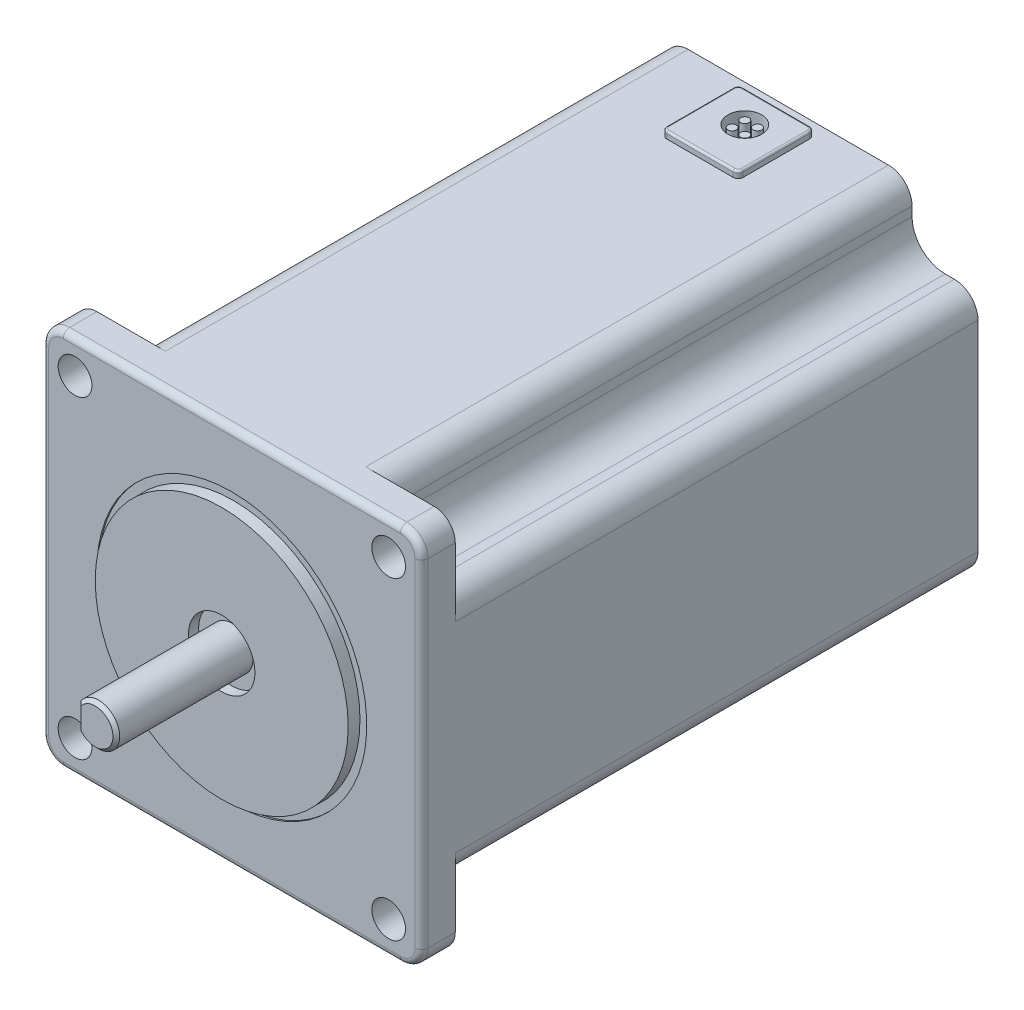
SolidWorks part; units mm, degrees
ref_plane "Front Plane" through (0, 0, 0) normal (0, 0, 1) x (1, 0, 0)
ref_plane "Top Plane" through (0, 0, 0) normal (0, 1, 0) x (1, 0, 0)
ref_plane "Right Plane" through (0, 0, 0) normal (1, 0, 0) x (0, 0, -1)
sketch "Sketch1" plane through (0, 0, 0) normal (0, 0, 1) x (1, 0, 0)
  line L0 (-2.667, -1.7227) -> (-2.667, 1.7227) construction
  line L1 (28.575, -28.575) -> (-28.575, -28.575) construction
  line L2 (28.575, -28.575) -> (28.575, 28.575) construction
  line L3 (28.575, 28.575) -> (-28.575, 28.575) construction
  line L4 (-28.575, -28.575) -> (-28.575, 28.575) construction
  line L5 (28.575, -28.575) -> (-28.575, 28.575) construction
  line L6 (28.575, 28.575) -> (-28.575, -28.575) construction
  line L7 (23.622, -23.622) -> (-23.622, -23.622) construction
  line L8 (23.622, -23.622) -> (23.622, 23.622) construction
  line L9 (23.622, 23.622) -> (-23.622, 23.622) construction
  line L10 (-23.622, -23.622) -> (-23.622, 23.622) construction
  line L11 (23.622, -23.622) -> (-23.622, 23.622) construction
  line L12 (23.622, 23.622) -> (-23.622, -23.622) construction
  circle A0 centre (-23.622, 23.622) radius 2.54 construction
  circle A1 centre (23.622, 23.622) radius 2.54 construction
  circle A2 centre (-23.622, -23.622) radius 2.54 construction
  circle A3 centre (23.622, -23.622) radius 2.54 construction
  circle A4 centre (0, 0) radius 3.175 construction
  circle A5 centre (0, 0) radius 19.05 construction
  point P0 (0, 0)
  point P6 (0, 0)
  point P18 (0, 3.175)
  point P19 (0, 28.575)
  point P20 (0, 19.05)
  point P21 (-23.622, -26.162)
  dimension "D3" = 5.08
  dimension "D4" = 6.35
  dimension "LargeDia" = 38.1
  dimension "Width" = 57.15
  dimension "CenterToCenter" = 47.244
  dimension "D6" = 5.842
sketch "Sketch2" plane through (0, 0, 0) normal (1, 0, 0) x (0, 0, -1)
  line L0 (0, 0) -> (78.74, 0) construction
  line L1 (0, 0) -> (-20.574, 0) construction
  line L2 (-20.574, -3.175) -> (-20.574, 3.175) construction
  line L3 (78.74, -28.575) -> (78.74, 28.575) construction
  line L4 (0, 28.575) -> (0, -28.575) construction
  line L5 (-1.524, 19.05) -> (-1.524, -19.05) construction
  line L6 (5.08, 28.575) -> (5.08, -28.575) construction
  point P3 (-1.524, 0)
  point P18 (5.08, 0)
  point P19 (-5.588, 0)
  dimension "Shaftlength" = 20.574
  dimension "D2" = 1.524
  dimension "D3" = 5.08
  dimension "D4" = 14.986
sketch "Sketch3" plane through (0, 0, 0) normal (0, 0, 1) x (1, 0, 0)
  line L1 (-28.575, -28.575) -> (-28.575, 28.575) construction
  line L2 (28.575, 28.575) -> (-28.575, 28.575) construction
  line L3 (28.575, -28.575) -> (28.575, 28.575) construction
  line L4 (28.575, -28.575) -> (-28.575, -28.575) construction
  line L5 (-28.575, -25.4) -> (-28.575, 25.4)
  line L6 (25.4, 28.575) -> (-25.4, 28.575)
  line L7 (28.575, -25.4) -> (28.575, 25.4)
  line L8 (25.4, -28.575) -> (-25.4, -28.575)
  arc A4 (-28.575, 25.4) -> (-25.4, 28.575) centre (-25.4, 25.4) cw
  arc A5 (25.4, 28.575) -> (28.575, 25.4) centre (25.4, 25.4) cw
  arc A6 (28.575, -25.4) -> (25.4, -28.575) centre (25.4, -25.4) cw
  arc A7 (-25.4, -28.575) -> (-28.575, -25.4) centre (-25.4, -25.4) cw
  dimension "D1" = 3.175
extrude "Boss-Extrude1" add sketch "Sketch3" against normal up to vertex (5.08 mm away) up to point (0, 0, -5.08)
fillet "Fillet1" radius 0.9906 8 edges at (0, 28.575, 0) (28.575, 0, 0) (0, -28.575, 0) (-28.575, 0, 0) (27.6451, 27.6451, 0) (27.6451, -27.6451, 0) (-27.6451, -27.6451, 0) (-27.6451, 27.6451, 0)
sketch "Sketch4" plane through (0, 0, -5.08) normal (0, 0, 1) x (1, 0, 0)
  line L0 (0, 28.575) -> (0, 0) construction
  line L1 (0, 0) -> (-28.575, 0) construction
  line L2 (-25.019, 18.6436) -> (-23.622, 18.6436)
  line L3 (-18.6436, 23.622) -> (-18.6436, 25.019)
  line L4 (-28.575, 25.4) -> (-28.575, -25.4)
  line L5 (25.4, 28.575) -> (-25.4, 28.575)
  line L6 (28.575, -25.4) -> (28.575, 25.4)
  line L7 (-25.4, -28.575) -> (25.4, -28.575)
  line L8 (-28.575, 15.0876) -> (-28.575, -15.0876)
  line L9 (15.0876, 28.575) -> (-15.0876, 28.575)
  line L10 (28.575, -15.0876) -> (28.575, 15.0876)
  line L14 (28.575, 28.575) -> (-28.575, 28.575) construction
  line L15 (18.6436, 23.622) -> (18.6436, 25.019)
  line L16 (25.019, 18.6436) -> (23.622, 18.6436)
  line L17 (25.019, -18.6436) -> (23.622, -18.6436)
  line L18 (18.6436, -23.622) -> (18.6436, -25.019)
  line L19 (15.0876, -28.575) -> (-15.0876, -28.575)
  line L20 (-18.6436, -23.622) -> (-18.6436, -25.019)
  line L21 (-25.019, -18.6436) -> (-23.622, -18.6436)
  arc A0 (-25.019, 18.6436) -> (-28.575, 15.0876) centre (-25.019, 15.0876) ccw
  arc A1 (-15.0876, 28.575) -> (-18.6436, 25.019) centre (-15.0876, 25.019) ccw
  arc A2 (-23.622, 18.6436) -> (-18.6436, 23.622) centre (-23.622, 23.622) ccw
  arc A3 (23.622, 18.6436) -> (18.6436, 23.622) centre (23.622, 23.622) cw
  arc A4 (-25.4, 28.575) -> (-28.575, 25.4) centre (-25.4, 25.4) ccw
  arc A5 (15.0876, 28.575) -> (18.6436, 25.019) centre (15.0876, 25.019) cw
  arc A6 (28.575, 25.4) -> (25.4, 28.575) centre (25.4, 25.4) ccw
  arc A7 (25.019, 18.6436) -> (28.575, 15.0876) centre (25.019, 15.0876) cw
  arc A8 (25.4, -28.575) -> (28.575, -25.4) centre (25.4, -25.4) ccw
  arc A10 (-28.575, -25.4) -> (-25.4, -28.575) centre (-25.4, -25.4) ccw
  arc A11 (25.019, -18.6436) -> (28.575, -15.0876) centre (25.019, -15.0876) ccw
  arc A12 (15.0876, -28.575) -> (18.6436, -25.019) centre (15.0876, -25.019) ccw
  arc A13 (23.622, -18.6436) -> (18.6436, -23.622) centre (23.622, -23.622) ccw
  arc A14 (-23.622, -18.6436) -> (-18.6436, -23.622) centre (-23.622, -23.622) cw
  arc A15 (-15.0876, -28.575) -> (-18.6436, -25.019) centre (-15.0876, -25.019) cw
  arc A16 (-25.019, -18.6436) -> (-28.575, -15.0876) centre (-25.019, -15.0876) cw
  dimension "D2" = 4.9784
  dimension "D3" = 3.556
  dimension "D1" = 0
extrude "Boss-Extrude2" add sketch "Sketch4" against normal blind 78.74
sketch "Sketch5" plane through (0, 0, 0) normal (1, 0, 0) x (0, 0, -1)
  line L1 (0, 0) -> (-1.524, 0)
  line L2 (0, 0) -> (0, 19.05)
  line L3 (0, 19.05) -> (-1.524, 19.05)
  line L4 (-1.524, 0) -> (-1.524, 19.05)
revolve "Revolve1" add sketch "Sketch5" angle 360 about L1
sketch "Sketch6" plane through (0, 0, 0) normal (1, 0, 0) x (0, 0, -1)
  line L0 (-20.574, 0) -> (-1.524, 0) construction
  line L1 (78.74, 0) -> (-1.524, 0)
  line L2 (78.74, 0) -> (78.74, 3.175)
  line L3 (0, 5) -> (-1.524, 5)
  line L4 (-1.524, 0) -> (-1.524, 5)
  line L5 (78.74, 3.175) -> (0, 3.175)
  line L6 (0, 3.175) -> (0, 5)
  line L10 (0, 20.32) -> (0.254, 20.32)
  line L11 (0, 20.32) -> (0, 19.05)
  line L12 (0, 19.05) -> (0.254, 19.05)
  line L13 (0.254, 20.32) -> (0.254, 19.05)
  dimension "D1" = 10
  dimension "D2" = 40.64
  dimension "D3" = 0.254
revolve "Cut-Revolve1" cut sketch "Sketch6" angle 360 about L0
sketch "Sketch7" plane through (0, 0, 0) normal (1, 0, 0) x (0, 0, -1)
  line L1 (-20.574, 3.175) -> (78.74, 3.175)
  line L2 (-20.574, 3.175) -> (-20.574, 0)
  line L3 (-20.574, 0) -> (78.74, 0)
  line L4 (78.74, 3.175) -> (78.74, 0)
revolve "Revolve2" add sketch "Sketch7" angle 360 about L3
sketch "Sketch8" plane through (0, 0, 20.574) normal (0, 0, 1) x (1, 0, 0)
  line L0 (-2.667, -1.7227) -> (-2.667, 1.7227) construction
  line L1 (-2.667, -1.7227) -> (-2.667, 1.7227)
  circle A0 centre (0, 0) radius 3.175 construction
  arc A1 (-2.667, 1.7227) -> (-2.667, -1.7227) centre (0, 0) ccw
extrude "Cut-Extrude1" cut sketch "Sketch8" against normal up to vertex (14.986 mm away) up to point (0, 0, 5.588)
chamfer "Chamfer1" distance 0.508 angle 45 3 edges at (0, -3.175, -78.74) (3.175, 0, 20.574) (-2.667, 0, 20.574)
sketch "Sketch9" plane through (0, 0, 0) normal (0, 0, 1) x (1, 0, 0)
  circle A0 centre (23.622, -23.622) radius 2.54 construction
  circle A1 centre (23.622, -23.622) radius 2.54
  circle A2 centre (-23.622, -23.622) radius 2.54 construction
  circle A3 centre (-23.622, 23.622) radius 2.54 construction
  circle A4 centre (23.622, 23.622) radius 2.54 construction
  circle A5 centre (-23.622, -23.622) radius 2.54
  circle A6 centre (-23.622, 23.622) radius 2.54
  circle A7 centre (23.622, 23.622) radius 2.54
extrude "Cut-Extrude2" cut sketch "Sketch9" against normal up to next (5.08 mm away)
sketch "Sketch10" plane through (0, 28.575, -0.7512) normal (0, 1, 0) x (1, 0, 0)
  line L0 (0, -0.7512) -> (0, 76.5207) construction
  line L2 (-3.8354, 76.5207) -> (-3.8354, 71.5677)
  line L3 (-3.8354, 71.5677) -> (3.8354, 71.5677)
  line L4 (3.8354, 76.5207) -> (3.8354, 71.5677)
  line L5 (25.4, -0.7512) -> (-25.4, -0.7512) construction
  line L7 (15.0876, 83.0688) -> (-15.0876, 83.0688) construction
  arc A0 (3.8354, 76.5207) -> (-3.8354, 76.5207) centre (0, 76.5207) ccw
  dimension "D1" = 7.6708
  dimension "D2" = 4.953
  dimension "D3" = 6.5481
extrude "Cut-Extrude3" cut sketch "Sketch10" against normal blind 1.2954
sketch "Sketch11" plane through (0, 27.2796, 0) normal (0, 1, 0) x (1, 0, 0)
  circle A0 centre (0, 77.2719) radius 2.54
  circle A1 centre (0, 77.2719) radius 3.7465
  dimension "D1" = 5.08
  dimension "D2" = 7.493
extrude "Boss-Extrude3" add sketch "Sketch11" along normal up to surface (1.2954 mm away) up to face at (0, 28.575, -75.7542)
sketch "Sketch12" plane through (0, 28.575, 0) normal (0, 1, 0) x (1, 0, 0)
  line L0 (0, 76.2686) -> (0, 0) construction
  line L1 (-5.7531, 70.5155) -> (5.7531, 70.5155)
  line L2 (-5.7531, 70.5155) -> (-5.7531, 82.0217)
  line L3 (-5.7531, 82.0217) -> (5.7531, 82.0217)
  line L4 (5.7531, 70.5155) -> (5.7531, 82.0217)
  line L5 (-5.7531, 70.5155) -> (5.7531, 82.0217) construction
  line L6 (-5.7531, 82.0217) -> (5.7531, 70.5155) construction
  circle A2 centre (0, 77.2719) radius 2.54 construction
  circle A3 centre (0, 77.2719) radius 2.54
  point P0 (0, 76.2686)
  dimension "D2" = 4.7498
  dimension "D1" = 11.5062
extrude "Boss-Extrude4" add sketch "Sketch12" along normal blind 1.016
fillet "Fillet2" radius 0.762 4 edges at (5.7531, 29.083, -82.0217) (-5.7531, 29.083, -82.0217) (5.7531, 29.083, -70.5155) (-5.7531, 29.083, -70.5155)
fillet "Fillet3" radius 0.3048 8 edges at (-5.5299, 29.591, -70.7387) (-5.7531, 29.591, -76.2686) (-5.5299, 29.591, -81.7985) (0, 29.591, -82.0217) (5.5299, 29.591, -81.7985) (5.7531, 29.591, -76.2686) (5.5299, 29.591, -70.7387) (0, 29.591, -70.5155)
sketch "Sketch13" plane through (0, 27.2796, 0) normal (0, 1, 0) x (1, 0, 0)
  line L4 (-0.9525, 76.3194) -> (0.9525, 76.3194) construction
  line L5 (-0.9525, 76.3194) -> (-0.9525, 78.2244) construction
  line L6 (-0.9525, 78.2244) -> (0.9525, 78.2244) construction
  line L7 (0.9525, 76.3194) -> (0.9525, 78.2244) construction
  line L8 (-0.9525, 76.3194) -> (0.9525, 78.2244) construction
  line L9 (-0.9525, 78.2244) -> (0.9525, 76.3194) construction
  circle A0 centre (-0.9525, 78.2244) radius 0.635
  circle A1 centre (0.9525, 78.2244) radius 0.635
  circle A2 centre (0.9525, 76.3194) radius 0.635
  circle A3 centre (-0.9525, 76.3194) radius 0.635
  circle A4 centre (0, 77.2719) radius 2.54 construction
  point P8 (0, 77.2719)
  dimension "D1" = 1.27
  dimension "D2" = 1.905
extrude "Boss-Extrude5" add sketch "Sketch13" along normal blind 1.9304
equation "\"D1@Boss-Extrude2\"=\"A@Sketch2\""
